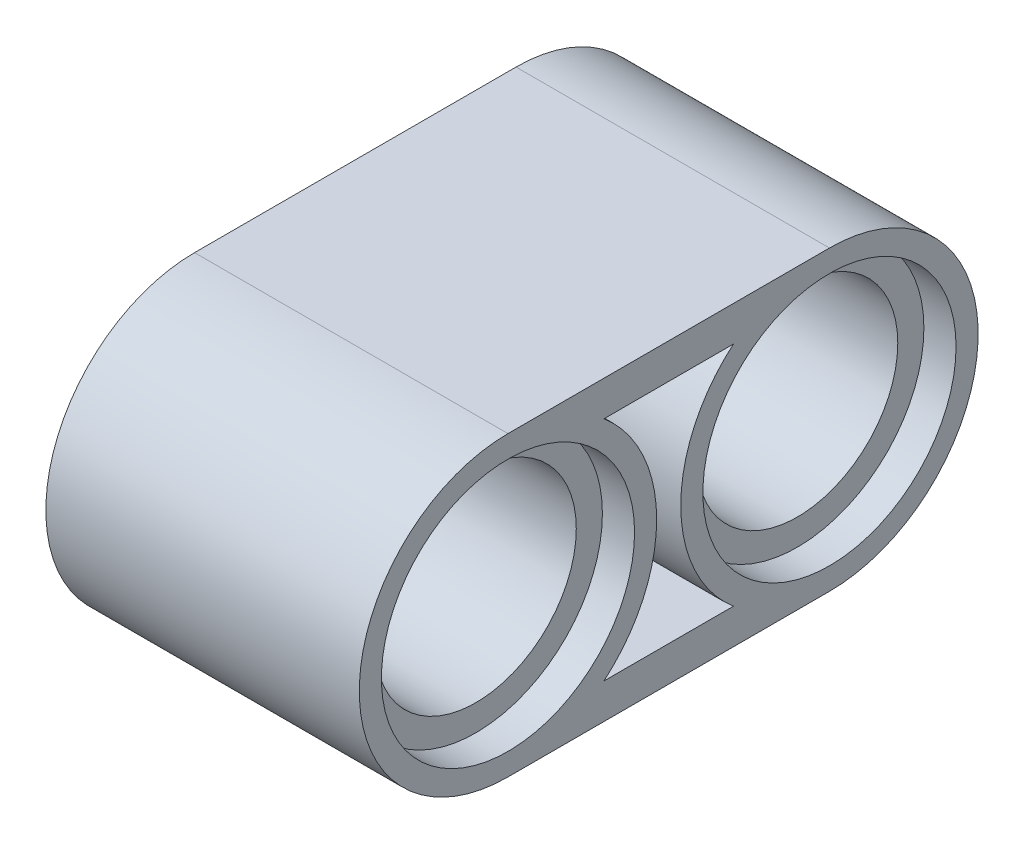
SolidWorks part; units mm, degrees
ref_plane "前视基准面" through (0, 0, 0) normal (0, 0, 1) x (1, 0, 0)
ref_plane "上视基准面" through (0, 0, 0) normal (0, 1, 0) x (1, 0, 0)
ref_plane "右视基准面" through (0, 0, 0) normal (1, 0, 0) x (0, 0, -1)
other "Configuration Table"
sketch "草图2" plane through (0, 0, 0) normal (1, 0, 0) x (0, 0, -1)
  line L0 (-4, 0) -> (4, 0) construction
  line L1 (-4, 3.7) -> (4, 3.7)
  line L2 (-4, -3.7) -> (4, -3.7)
  arc A0 (-4, 3.7) -> (-4, -3.7) centre (-4, 0) ccw
  arc A1 (4, -3.7) -> (4, 3.7) centre (4, 0) ccw
  circle A2 centre (-4, 0) radius 2.5
  circle A3 centre (-4, 0) radius 3.15
  circle A4 centre (4, 0) radius 2.5
  circle A5 centre (4, 0) radius 3.15
  point P3 (0, 0)
  dimension "D2" = 5
  dimension "D4" = 8
  dimension "D3" = 6.3
  dimension "D1" = 7.4
extrude "凸台-拉伸1" add sketch "草图2" along normal blind 7.8 contours A2 | A2 A3 | A4 | A5 A4 | L2 A1 L1 A0 A3 A5 region at (0, 0, 0) region at (0, 0, 4) region at (0, 0, 7.0609) region at (0, 0, -4) region at (0, 0, -0.9391)
extrude "切除-拉伸1" cut sketch "草图2<3>" against normal through all and the other way through all contours A2 | A4 region at (0, 0, 4) region at (0, 0, -4)
sketch "草图2<3>" plane through (0, 0, 0) normal (1, 0, 0) x (0, 0, -1) same geometry as "草图2"
extrude "切除-拉伸6" cut sketch "草图2<6>" along normal blind 1 contours A5 A4 | A2 A3 region at (0, 0, 7.0609) region at (0, 0, -0.9391)
sketch "草图2<6>" plane through (0, 0, 0) normal (1, 0, 0) x (0, 0, -1) same geometry as "草图2"
ref_plane "基准面1" through (4, 0, 0) normal (1, 0, 0) x (0, 0, -1)
mirror "镜向1" about plane through (4, 0, 0) normal (1, 0, 0) of "切除-拉伸6"
sketch "草图3" plane through (7.8, 0, 0) normal (1, 0, 0) x (0, 0, -1)
  line L11 (-4, 2.825) -> (4, 2.825)
  line L12 (-4, 3.15) -> (4, 3.15) construction
  line L13 (-4, 3.15) -> (-4, 2.5) construction
  line L14 (-4, 2.5) -> (4, 2.5) construction
  line L15 (4, 3.15) -> (4, 2.5) construction
  line L16 (-4, -2.5) -> (4, -2.5) construction
  line L17 (-4, -2.5) -> (-4, -3.15) construction
  line L18 (-4, -3.15) -> (4, -3.15) construction
  line L19 (4, -2.5) -> (4, -3.15) construction
  line L20 (-4, -2.825) -> (4, -2.825)
  circle A7 centre (-4, 0) radius 3.7
  arc A8 (-4, 3.7) -> (-4, -3.7) centre (-4, 0) ccw construction
  circle A9 centre (4, 0) radius 3.7
  arc A10 (4, -3.7) -> (4, 3.7) centre (4, 0) ccw construction
  circle A11 centre (-4, 0) radius 3.15 construction
  circle A12 centre (4, 0) radius 2.5 construction
  circle A13 centre (-4, 0) radius 2.5 construction
  circle A14 centre (4, 0) radius 3.15 construction
  point P27 (-4, 2.825)
  point P28 (-4, -2.825)
  point P32 (4, 2.825)
  point P33 (4, -2.825)
extrude "切除-拉伸7" cut sketch "草图3" against normal blind 2 contours A9 L11 A7 L20 region at (7.8, 0, 0)
extrude "切除-拉伸8" cut sketch "草图3<3>" along normal blind 2 from surface contours A9 L11 A7 L20 region at (7.8, 0, 0) starting at face at (0, 0, 0.85)
sketch "草图3<3>" plane through (7.8, 0, 0) normal (1, 0, 0) x (0, 0, -1) same geometry as "草图3"
